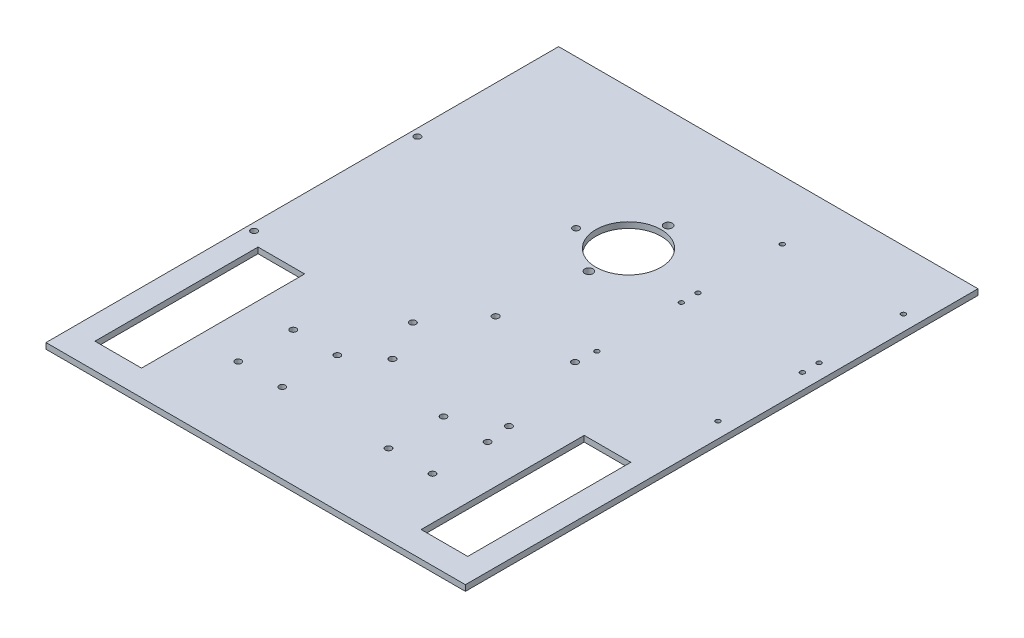
SolidWorks part; units mm, degrees
ref_plane "Front Plane" through (0, 0, 0) normal (0, 0, 1) x (1, 0, 0)
ref_plane "Top Plane" through (0, 0, 0) normal (0, 1, 0) x (1, 0, 0)
ref_plane "Right Plane" through (0, 0, 0) normal (1, 0, 0) x (0, 0, -1)
sketch "Sketch1" plane through (0, 0, 0) normal (0, 1, 0) x (1, 0, 0)
  line L0 (114.3, 279.4) -> (114.3, 0) construction
  line L1 (0, 0) -> (228.6, 0)
  line L2 (0, 0) -> (0, 279.4)
  line L3 (0, 279.4) -> (228.6, 279.4)
  line L4 (228.6, 0) -> (228.6, 279.4)
  line L5 (0, 50.8) -> (228.6, 50.8) construction
  line L6 (0, 190.5) -> (228.6, 190.5) construction
  dimension "D1" = 228.6
  dimension "D2" = 279.4
  dimension "D3" = 50.8
  dimension "D4" = 139.7
extrude "Boss-Extrude1" add sketch "Sketch1" along normal blind 3.175
sketch "Sketch3" plane through (0, 3.175, 0) normal (0, 1, 0) x (1, 0, 0)
  line L0 (114.3, 279.4) -> (114.3, 0) construction
  line L1 (228.6, 279.4) -> (0, 279.4) construction
  line L2 (0, 0) -> (228.6, 0) construction
  line L3 (0, 58.42) -> (228.6, 58.42) construction
  line L4 (0, 279.4) -> (0, 0) construction
  line L5 (228.6, 0) -> (228.6, 279.4) construction
  line L6 (215.9, 13.97) -> (190.5, 13.97)
  line L7 (12.7, 13.97) -> (38.1, 13.97)
  line L8 (12.7, 13.97) -> (12.7, 102.87)
  line L9 (12.7, 102.87) -> (38.1, 102.87)
  line L10 (38.1, 13.97) -> (38.1, 102.87)
  line L11 (12.7, 13.97) -> (38.1, 102.87) construction
  line L12 (12.7, 102.87) -> (38.1, 13.97) construction
  line L13 (53.34, 38.42) -> (93.34, 38.42) construction
  line L14 (53.34, 38.42) -> (53.34, 78.42) construction
  line L15 (53.34, 78.42) -> (93.34, 78.42) construction
  line L16 (93.34, 38.42) -> (93.34, 78.42) construction
  line L17 (53.34, 38.42) -> (93.34, 78.42) construction
  line L18 (53.34, 78.42) -> (93.34, 38.42) construction
  line L19 (190.5, 13.97) -> (190.5, 102.87)
  line L20 (215.9, 13.97) -> (215.9, 102.87)
  line L21 (215.9, 102.87) -> (190.5, 102.87)
  circle A0 centre (85.34, 43.42) radius 1.7
  circle A1 centre (61.34, 43.42) radius 1.7
  circle A2 centre (85.34, 73.42) radius 1.7
  circle A3 centre (61.34, 73.42) radius 1.7
  circle A4 centre (167.26, 73.42) radius 1.7
  circle A5 centre (143.26, 73.42) radius 1.7
  circle A6 centre (167.26, 43.42) radius 1.7
  circle A7 centre (143.26, 43.42) radius 1.7
  point P32 (25.4, 58.42)
  point P37 (73.34, 58.42)
  dimension "D1" = 3.4
  dimension "D2" = 3.4
  dimension "D3" = 3.4
  dimension "D4" = 3.4
  dimension "D5" = 15
  dimension "D6" = 25.4
  dimension "D7" = 88.9
  dimension "D8" = 40
  dimension "D9" = 40
  dimension "D10" = 8
  dimension "6" = 27.94
extrude "Cut-Extrude1" cut sketch "Sketch3" against normal through all
sketch "Sketch4" plane through (0, 3.175, 0) normal (0, 1, 0) x (1, 0, 0)
  circle A0 centre (114.3, 203.2) radius 17.78
  circle A1 centre (114.3, 224.79) radius 2.25
  circle A2 centre (114.3, 181.61) radius 2.25
extrude "Cut-Extrude2" cut sketch "Sketch4" against normal through all
sketch "Sketch5" plane through (0, 3.175, 0) normal (0, 1, 0) x (1, 0, 0)
  circle A0 centre (90.5, 198.41) radius 1.75
  circle A1 centre (90.5, 109.41) radius 1.75
  circle A2 centre (4, 109.41) radius 1.75
  circle A3 centre (4, 198.41) radius 1.75
extrude "Cut-Extrude3" cut sketch "Sketch5" against normal through all
sketch "Sketch6" plane through (0, 3.175, 0) normal (0, 1, 0) x (1, 0, 0)
  circle A0 centre (154.25, 247.1021) radius 1.25
  circle A1 centre (220.25, 247.1021) radius 1.25
  circle A2 centre (220.25, 201.1021) radius 1.25
  circle A3 centre (154.25, 201.1021) radius 1.25
  circle A4 centre (220.25, 192.0221) radius 1.25
  circle A5 centre (220.25, 146.0221) radius 1.25
  circle A6 centre (154.25, 146.0221) radius 1.25
  circle A7 centre (154.25, 192.0221) radius 1.25
extrude "Cut-Extrude4" cut sketch "Sketch6" against normal through all
sketch "Sketch7" plane through (0, 3.175, 0) normal (0, 1, 0) x (1, 0, 0)
  circle A0 centre (110.1555, 134.9346) radius 1.75
  circle A1 centre (153.3955, 134.9346) radius 1.75
  circle A2 centre (102.1555, 86.6946) radius 1.75
  circle A3 centre (165.5955, 86.6946) radius 1.75
extrude "Cut-Extrude5" cut sketch "Sketch7" against normal through all
